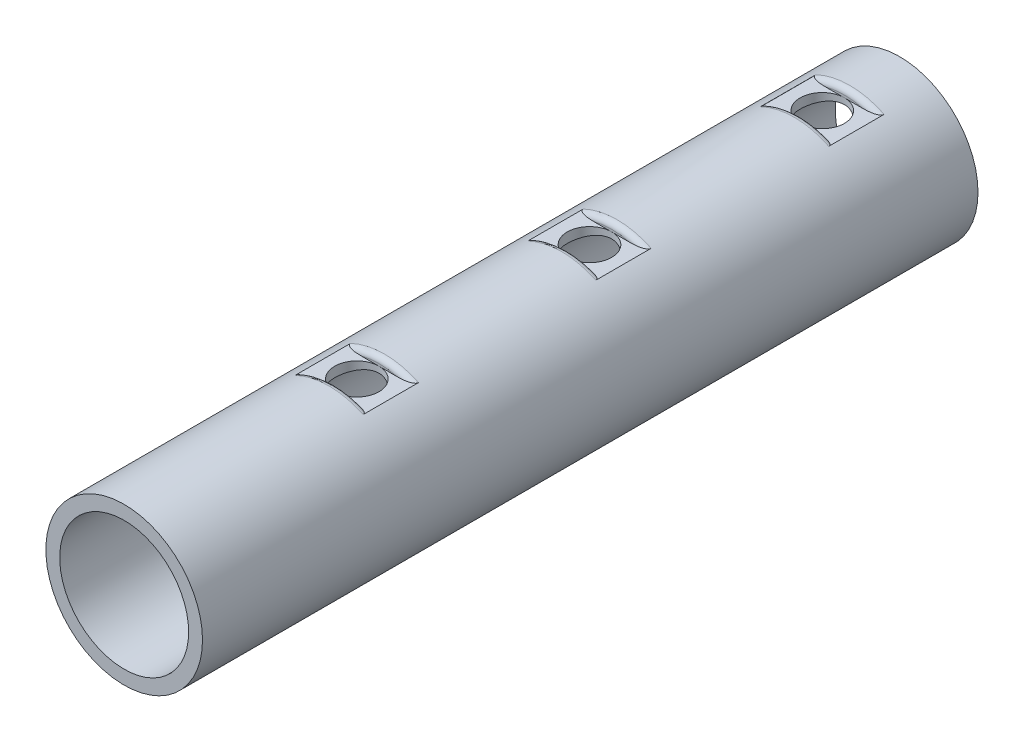
SolidWorks part; units mm, degrees
ref_plane "Front Plane" through (0, 0, 0) normal (0, 0, 1) x (1, 0, 0)
ref_plane "Top Plane" through (0, 0, 0) normal (0, 1, 0) x (1, 0, 0)
ref_plane "Right Plane" through (0, 0, 0) normal (1, 0, 0) x (0, 0, -1)
sketch "Sketch1" plane through (0, 0, 0) normal (0, 0, 1) x (1, 0, 0)
  circle A0 centre (0, 0) radius 14.14
  circle A2 centre (0, 0) radius 11.64
  dimension "D1" = 28.28
  dimension "D2" = 2.5
extrude "Boss-Extrude1" add sketch "Sketch1" along normal blind 140
ref_plane "Plane1" through (0, 0, 10) normal (0, 0, -1) x (-1, 0, 0)
sketch "Sketch2" plane through (0, 0, 10) normal (0, 0, -1) x (-1, 0, 0)
  line L0 (0, 12.71) -> (20.0782, 12.71) construction
  line L1 (0, -14.14) -> (21.6123, -14.14) construction
  line L3 (6.1363, 12.71) -> (-6.1964, 12.71)
  line L4 (6.1363, 12.71) -> (6.1363, 15.6114)
  line L5 (6.1363, 15.6114) -> (-6.1964, 15.6114)
  line L6 (-6.1964, 12.71) -> (-6.1964, 15.6114)
  circle A0 centre (0, 0) radius 14.14 construction
  point P10 (0, 0)
  dimension "D1" = 26.85
extrude "Cut-Extrude1" cut sketch "Sketch2" against normal blind 8
sketch "Sketch3" plane through (0, 12.71, 0) normal (0, 1, 0) x (1, 0, 0)
  line L0 (6.1964, -18) -> (-6.1363, -10) construction
  line L1 (15.554, -10) -> (-15.554, -10) construction
  line L2 (-6.1363, -18) -> (-6.1363, -10) construction
  line L3 (-6.1363, -10) -> (-6.1363, -14) construction
  line L4 (-6.1363, -14) -> (6.1964, -14) construction
  line L5 (6.1964, -18) -> (6.1964, -10) construction
  circle A0 centre (0.0301, -14) radius 4
extrude "Cut-Extrude2" cut sketch "Sketch3" against normal blind 10
fillet "Fillet1" radius 1 2 edges at (0.0334, 14.14, 10) (0.0334, 14.14, 18)
ref_plane "Plane2" through (0, 0, 14) normal (0, 0, -1) x (-1, 0, 0)
ref_plane "Plane3" through (0, 0, 56) normal (0, 0, -1) x (-1, 0, 0)
sketch "Sketch4" plane through (0, 0, 56) normal (0, 0, -1) x (-1, 0, 0)
  line L6 (0, -14.14) -> (14.14, -14.14) construction
  line L7 (0.9096, 12.71) -> (21.5058, 12.71) construction
  line L9 (6.1363, 12.7391) -> (-6.1363, 12.7391)
  line L10 (6.1363, 12.7391) -> (6.1363, 15.731)
  line L11 (6.1363, 15.731) -> (-6.1363, 15.731)
  line L12 (-6.1363, 12.7391) -> (-6.1363, 15.731)
  circle A1 centre (0, 0) radius 14.14 construction
  point P19 (0, 0)
  dimension "D2" = 26.85
extrude "Cut-Extrude3" cut sketch "Sketch4" against normal mid plane 8
sketch "Sketch5" plane through (0, 12.7391, 0) normal (0, 1, 0) x (1, 0, 0)
  line L0 (-6.1363, -56) -> (6.1363, -56) construction
  line L1 (-6.1363, -60) -> (-6.1363, -52) construction
  line L2 (6.1363, -60) -> (6.1363, -52) construction
  circle A0 centre (0, -56) radius 4
extrude "Cut-Extrude4" cut sketch "Sketch5" against normal mid plane 8
fillet "Fillet2" radius 1 2 edges at (0, 14.14, 60) (0, 14.14, 52)
pattern_linear "LPattern1" count 2 spacing 42 along (0, 0, 1) of "Cut-Extrude3", "Cut-Extrude4", "Fillet2"
